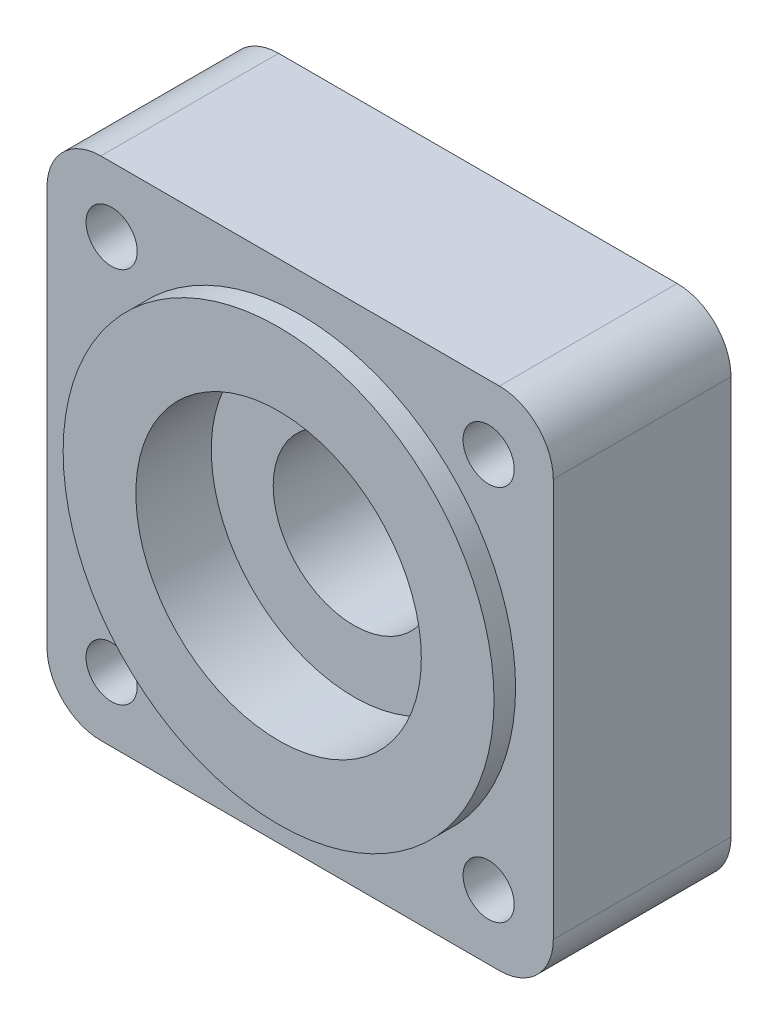
SolidWorks part; units mm, degrees
ref_plane "Front Plane" through (0, 0, 0) normal (0, 0, 1) x (1, 0, 0)
ref_plane "Top Plane" through (0, 0, 0) normal (0, 1, 0) x (1, 0, 0)
ref_plane "Right Plane" through (0, 0, 0) normal (1, 0, 0) x (0, 0, -1)
sketch "Sketch2" plane through (0, 0, 0) normal (0, 0, 1) x (1, 0, 0)
  line L1 (-67.7353, 44.9265) -> (26.2647, 44.9265)
  line L2 (-67.7353, 44.9265) -> (-67.7353, -49.0735)
  line L3 (-67.7353, -49.0735) -> (26.2647, -49.0735)
  line L4 (26.2647, 44.9265) -> (26.2647, -49.0735)
  dimension "D1" = 94
  dimension "D2" = 94
extrude "Boss-Extrude1" add sketch "Sketch2" along normal blind 33
sketch "Sketch3" plane through (0, 0, 0) normal (0, 0, 1) x (1, 0, 0)
  line L0 (-20.7353, 44.9265) -> (-20.7353, -49.0735) construction
  line L1 (26.2647, 44.9265) -> (-67.7353, 44.9265) construction
  line L2 (-67.7353, -49.0735) -> (26.2647, -49.0735) construction
  line L3 (-67.7353, -2.0735) -> (26.2647, -2.0735) construction
  line L4 (-67.7353, 44.9265) -> (-67.7353, -49.0735) construction
  line L5 (26.2647, -49.0735) -> (26.2647, 44.9265) construction
  circle A0 centre (-20.7353, -2.0735) radius 23.5
  dimension "D1" = 47
extrude "Boss-Extrude2" add sketch "Sketch3" against normal blind 2 separate body
sketch "Sketch5" plane through (0, 0, 0) normal (0, 0, 1) x (1, 0, 0)
  line L0 (-20.7353, 44.9265) -> (-20.7353, -49.0735) construction
  line L1 (26.2647, 44.9265) -> (-67.7353, 44.9265) construction
  line L2 (-67.7353, -49.0735) -> (26.2647, -49.0735) construction
  circle A0 centre (-20.7353, -2.0735) radius 15
  dimension "D1" = 30
extrude "Cut-Extrude1" cut sketch "Sketch5" along normal through all and the other way through all
ref_plane "Plane1" through (0, 0, 33) normal (0, 0, 1) x (1, 0, 0)
sketch "Sketch6" plane through (0, 0, 33) normal (0, 0, 1) x (1, 0, 0)
  circle A0 centre (-20.7353, -2.0735) radius 26.5
  dimension "D1" = 53
sketch "Sketch7" plane through (0, 0, 33) normal (0, 0, 1) x (1, 0, 0)
  circle A0 centre (-20.7353, -2.0735) radius 40
  dimension "D1" = 80
extrude "Boss-Extrude3" add sketch "Sketch7" along normal blind 4
extrude "Cut-Extrude3" cut sketch "Sketch6" against normal blind 10 and the other way through all
sketch "Sketch8" plane through (0, 0, 0) normal (0, 0, 1) x (1, 0, 0)
  line L0 (-67.7353, -2.0735) -> (-67.7353, -0.0735)
  line L1 (26.2647, 44.9265) -> (-67.7353, 44.9265) construction
  line L3 (-18.7353, 44.9265) -> (-18.7353, 21.3412)
  line L4 (-22.7353, 44.9265) -> (-22.7353, 21.3412)
  line L5 (-18.7353, 44.9265) -> (-22.7353, 44.9265)
  line L7 (-22.7353, -49.0735) -> (-22.7353, -25.2306)
  line L8 (-18.7353, -49.0735) -> (-22.7353, -49.0735)
  line L9 (-18.7353, -49.0735) -> (-18.7353, -25.2306)
  line L10 (-67.7353, 44.9265) -> (-67.7353, -49.0735) construction
  line L11 (-20.7353, -2.0735) -> (-67.7353, -2.0735) construction
  line L12 (-67.7353, -2.0735) -> (-67.7353, -4.0735)
  line L13 (-67.7353, -0.0735) -> (-44.15, -0.0735)
  line L14 (-67.7353, -4.0735) -> (-44.15, -4.0735)
  line L15 (-20.7353, -2.0735) -> (-20.7353, 21.4265) construction
  line L16 (26.2647, -2.0735) -> (26.2647, -4.0735)
  line L17 (26.2647, -4.0735) -> (2.6794, -4.0735)
  line L18 (26.2647, -2.0735) -> (26.2647, -0.0735)
  line L19 (26.2647, -0.0735) -> (2.6794, -0.0735)
  circle A3 centre (-20.7353, -2.0735) radius 23.5 construction
  circle A4 centre (-20.7353, -2.0735) radius 23.5
  point P28 (-20.7353, 44.9265)
  point P29 (-20.7353, -49.0735)
  dimension "D2" = 2
  dimension "D3" = 2
  dimension "D1" = 2
  dimension "D4" = 2
sketch "Sketch11" plane through (0, 0, 0) normal (0, 0, 1) x (1, 0, 0)
  line L0 (26.2647, -49.0735) -> (26.2647, 44.9265) construction
  line L1 (-18.7353, 44.9265) -> (-22.7353, 44.9265) construction
  line L2 (-67.7353, -49.0735) -> (26.2647, -49.0735) construction
  circle A0 centre (14.2647, 32.9265) radius 6.5
  circle A1 centre (14.2647, -37.0735) radius 6.5
  circle A2 centre (14.2647, -37.0735) radius 6.5
  circle A3 centre (-55.7353, -37.0735) radius 6.5
  circle A4 centre (-55.7353, 32.9265) radius 6.5
  point P6 (-20.7353, 44.9265)
  point P20 (-20.7353, -2.0735)
  dimension "D2" = 13
  dimension "D5" = 13
  dimension "D8" = 4
  dimension "D1" = 12
  dimension "D3" = 35
  dimension "D4" = 70
  dimension "D6" = 12
  dimension "D7" = 12
sketch "Sketch10" plane through (0, 0, 0) normal (0, 0, 1) x (1, 0, 0)
  line L0 (-18.7353, 21.3412) -> (-18.7353, 41.9265)
  line L1 (2.6794, -0.0735) -> (23.2647, -0.0735)
  line L2 (-18.7353, 44.9265) -> (-18.7353, 21.3412) construction
  line L3 (26.2647, -0.0735) -> (2.6794, -0.0735) construction
  line L4 (23.2647, -0.0735) -> (23.2647, 24.9265)
  line L5 (-18.7353, 41.9265) -> (6.2647, 41.9265)
  line L6 (26.2647, 44.9265) -> (-67.7353, 44.9265) construction
  line L7 (-20.7353, 21.4265) -> (-20.7353, -2.0735) construction
  line L8 (-20.7353, -2.0735) -> (-35.7661, -2.0735) construction
  line L11 (-20.7353, -2.0735) -> (-67.7353, -2.0735) construction
  line L12 (2.6794, -4.0735) -> (23.2647, -4.0735)
  line L14 (23.2647, -4.0735) -> (23.2647, -29.0735)
  line L15 (-18.7353, -25.4883) -> (-18.7353, -46.0735)
  line L16 (-18.7353, -46.0735) -> (6.2647, -46.0735)
  line L17 (-22.7353, 21.3412) -> (-22.7353, 41.9265)
  line L18 (-22.7353, 41.9265) -> (-47.7353, 41.9265)
  line L19 (-64.7353, -0.0735) -> (-64.7353, 24.9265)
  line L20 (-44.15, -0.0735) -> (-64.7353, -0.0735)
  line L21 (-44.15, -4.0735) -> (-64.7353, -4.0735)
  line L22 (-64.7353, -4.0735) -> (-64.7353, -29.0735)
  line L23 (-22.7353, -25.4883) -> (-22.7353, -46.0735)
  line L24 (-22.7353, -46.0735) -> (-47.7353, -46.0735)
  arc A0 (16.9529, 24.8725) -> (23.2647, 24.9265) centre (20.1362, 21.6919) cw
  arc A1 (6.2647, 41.9265) -> (6.2647, 35.9265) centre (2.9106, 38.9265) cw
  arc A2 (16.9529, 24.8725) -> (6.2647, 35.9265) centre (14.5363, 33.2302) cw
  arc A3 (6.2647, -46.0735) -> (6.2647, -40.0735) centre (2.9106, -43.0735) ccw
  circle A4 centre (-20.7353, -2.0735) radius 23.5 construction
  arc A5 (16.9529, -29.0196) -> (6.2647, -40.0735) centre (14.5363, -37.3772) ccw
  arc A6 (16.9529, -29.0196) -> (23.2647, -29.0735) centre (20.1362, -25.8389) ccw
  arc A7 (-58.4235, -29.0196) -> (-64.7353, -29.0735) centre (-61.6068, -25.8389) cw
  arc A8 (-47.7353, 41.9265) -> (-47.7353, 35.9265) centre (-44.3812, 38.9265) ccw
  arc A9 (-58.4235, 24.8725) -> (-64.7353, 24.9265) centre (-61.6068, 21.6919) ccw
  arc A10 (-58.4235, 24.8725) -> (-47.7353, 35.9265) centre (-56.0069, 33.2302) ccw
  arc A11 (-47.7353, -46.0735) -> (-47.7353, -40.0735) centre (-44.3812, -43.0735) cw
  arc A12 (-58.4235, -29.0196) -> (-47.7353, -40.0735) centre (-56.0069, -37.3772) cw
  circle A13 centre (-20.7353, -2.0735) radius 23.5
  point P15 (23.2647, 44.9265)
  dimension "D3" = 12
  dimension "D4" = 33
  dimension "D10" = 8.7
  dimension "D1" = 3
  dimension "D2" = 3
  dimension "D5" = 25
  dimension "D6" = 25
extrude "Cut-Extrude4" cut sketch "Sketch10" along normal blind 7.5 contours A13 L1 L4 A0 A2 A1 L5 L0 | A13 L17 L18 A8 A10 A9 L19 L20 | A13 L21 L22 A7 A12 A11 L24 L23 | A13 L15 L16 A3 A5 A6 L14 L12 region at (2.8905, 21.543, 0) region at (-44.3611, 21.543, 0) region at (2.8905, -25.69, 0) region at (-44.3611, -25.69, 0)
ref_plane "Plane2" through (-18.7353, 0, 0) normal (1, 0, 0) x (0, 0, -1)
sketch "Sketch12" plane through (-18.7353, 0, 0) normal (1, 0, 0) x (0, 0, -1)
  line L0 (-3.75, 41.9265) -> (0, 41.9265) construction
  line L1 (-7.5, 41.9265) -> (0, 41.9265) construction
  line L2 (0, 41.9265) -> (0, 34.5827) construction
  line L3 (0, 21.3412) -> (0, 41.9265) construction
  line L4 (0, 21.3412) -> (0, 34.5827) construction
  line L5 (0, 21.3412) -> (-7.5, 21.3412) construction
  line L6 (-7.5, 21.3412) -> (-7.5, 41.9265) construction
  line L7 (-7.5, 41.9265) -> (-3.75, 41.9265) construction
  line L8 (-2.3946, 41.9265) -> (0, 21.3412)
  line L9 (-2.3946, 41.9265) -> (0, 41.9265)
  line L10 (0, 41.9265) -> (0, 21.3412)
  line L11 (-7.5, -2.0735) -> (10.9159, -2.0735) construction
  line L12 (-7.5, 41.9265) -> (-7.5, -46.0735) construction
  line L13 (-7.5, -46.0735) -> (-3.75, -46.0735) construction
  line L14 (0, -25.4883) -> (0, -38.7298) construction
  line L15 (0, -46.0735) -> (0, -38.7298) construction
  line L16 (-3.75, -46.0735) -> (0, -46.0735) construction
  line L17 (0, -46.0735) -> (0, -25.4883)
  line L18 (-2.3946, -46.0735) -> (0, -46.0735)
  line L19 (-2.3946, -46.0735) -> (0, -25.4883)
  dimension "D1" = 20.7241
extrude "Cut-Extrude6" cut sketch "Sketch12" against normal blind 4
ref_plane "Plane3" through (0, -0.0735, 0) normal (0, 1, 0) x (1, 0, 0)
sketch "Sketch13" plane through (0, -0.0735, 0) normal (0, 1, 0) x (1, 0, 0)
  line L0 (-64.7353, -4.78) -> (-64.7353, 0) construction
  line L3 (-64.7353, -7.5) -> (-64.7353, 0) construction
  line L4 (-67.7353, 0) -> (-44.15, 0) construction
  line L5 (-64.7353, 0) -> (-44.15, 0) construction
  line L6 (-64.7353, -2.39) -> (-44.15, 0)
  line L7 (-64.7353, -2.39) -> (-64.7353, 0)
  line L8 (-64.7353, 0) -> (-44.15, 0)
  line L9 (-64.7353, -7.5) -> (23.2647, -7.5) construction
  line L10 (-20.7353, -7.5) -> (-20.7353, 41.4234) construction
  line L11 (23.2647, 0) -> (2.6794, 0) construction
  line L12 (23.2647, -4.78) -> (23.2647, 0) construction
  line L13 (23.2647, 0) -> (2.6794, 0)
  line L14 (23.2647, -2.39) -> (23.2647, 0)
  line L15 (23.2647, -2.39) -> (2.6794, 0)
  line L16 (23.2647, -2.39) -> (23.2647, 0)
  line L17 (-64.7353, 0) -> (-44.15, 0)
  line L18 (2.6794, 0) -> (23.2647, 0)
  dimension "D1" = 2.39
extrude "Cut-Extrude7" cut sketch "Sketch13" against normal blind 4 contours L15 L14 L13 | L8 L7 L6 region at (-57.8735, -0.0735, 0.7967) region at (16.403, -0.0735, 0.7967)
extrude "Cut-Extrude8" cut sketch "Sketch11" along normal blind 10 contours A0 | A4 | A1 | A3 region at (14.2647, 32.9265, 0) region at (14.2647, -37.0735, 0) region at (-55.7353, 32.9265, 0)
sketch "Sketch14" plane through (0, 0, 0) normal (0, 0, 1) x (1, 0, 0)
  circle A0 centre (-55.7353, 32.9265) radius 4.75
  circle A1 centre (14.2647, 32.9265) radius 4.75
  circle A2 centre (14.2647, -37.0735) radius 4.75
  circle A3 centre (-55.7353, -37.0735) radius 4.75
  point P12 (-20.7353, -2.0735)
  dimension "D1" = 9.5
  dimension "D2" = 4
extrude "Cut-Extrude9" cut sketch "Sketch14" along normal through all
fillet "Fillet4" radius 10 4 edges at (26.2647, -49.0735, 16.5) (-67.7353, -49.0735, 16.5) (-67.7353, 44.9265, 16.5) (26.2647, 44.9265, 16.5)
fillet "Fillet7" radius 10 1 edges at (23.2647, -0.0735, 4.945)
fillet "Fillet8" radius 10 1 edges at (23.2647, -4.0735, 4.945)
fillet "Fillet9" radius 10 2 edges at (-64.7353, -4.0735, 4.945) (-64.7353, -0.0735, 4.945)
fillet "Fillet10" radius 10 2 edges at (-18.7353, 41.9265, 4.9473) (-22.7353, 41.9265, 4.9473)
fillet "Fillet11" radius 10 2 edges at (-22.7353, -46.0735, 4.9473) (-18.7353, -46.0735, 4.9473)
fillet "Fillet12" radius 10 1 edges at (-20.7353, -46.0735, 2.3946)
fillet "Fillet13" radius 10 3 edges at (-20.7353, 41.9265, 2.3946) (-64.7353, -2.0735, 2.39) (23.2647, -2.0735, 2.39)
sketch "Sketch15" plane through (0, 0, -2) normal (0, 0, -1) x (-1, 0, 0)
  line L0 (20.7353, 21.4265) -> (20.7353, -25.5735) construction
  circle A0 centre (20.7353, -2.0735) radius 23.5 construction
  circle A1 centre (20.7353, -2.0735) radius 20
  dimension "D1" = 40
extrude "Cut-Extrude10" cut sketch "Sketch15" against normal blind 1
fillet "Fillet14" radius 10 1 edges at (-40.7353, -2.0735, -1)
